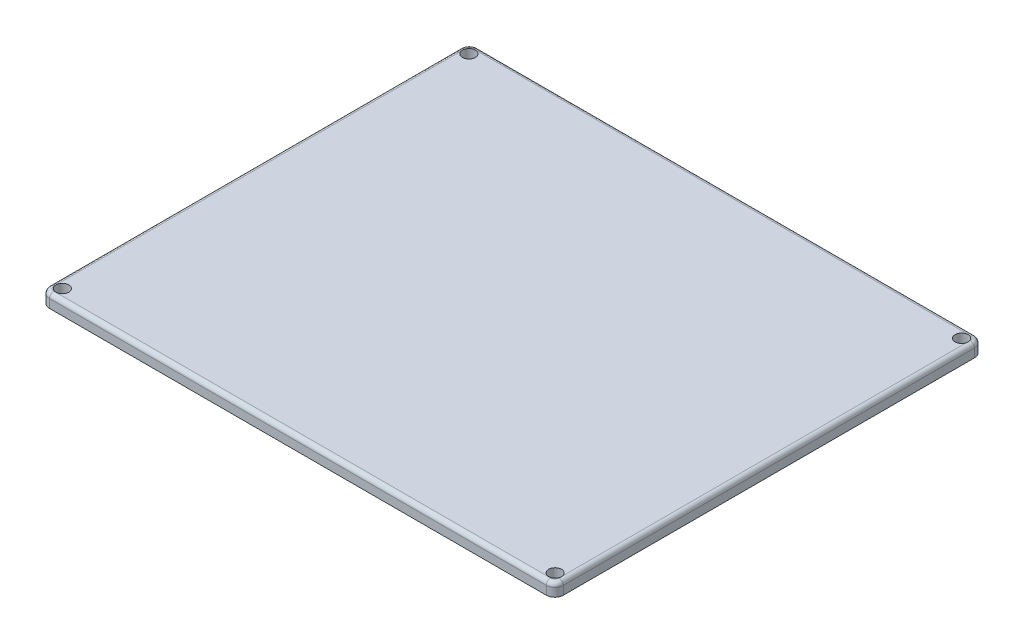
SolidWorks part; units mm, degrees
ref_plane "Front Plane" through (0, 0, 0) normal (0, 0, 1) x (1, 0, 0)
ref_plane "Top Plane" through (0, 0, 0) normal (0, 1, 0) x (1, 0, 0)
ref_plane "Right Plane" through (0, 0, 0) normal (1, 0, 0) x (0, 0, -1)
sketch "Sketch1" plane through (0, 0, 0) normal (0, 1, 0) x (1, 0, 0)
  line L1 (-60, 50) -> (60, 50)
  line L2 (-60, 50) -> (-60, -50)
  line L3 (-60, -50) -> (60, -50)
  line L4 (60, 50) -> (60, -50)
  line L5 (-60, 50) -> (60, -50) construction
  line L6 (-60, -50) -> (60, 50) construction
  point P0 (0, 0)
  dimension "D1" = 120
  dimension "D2" = 100
extrude "Boss-Extrude1" add sketch "Sketch1" along normal blind 3
sketch "Sketch2" plane through (0, 0, 0) normal (0, -1, 0) x (-1, 0, 0)
  line L0 (0, 50) -> (0, -50) construction
  line L1 (-60, 50) -> (60, 50) construction
  line L2 (60, -50) -> (-60, -50) construction
  line L3 (60, 0) -> (-60, 0) construction
  line L4 (60, 50) -> (60, -50) construction
  line L5 (-60, -50) -> (-60, 50) construction
  circle A0 centre (57.529, -47.4651) radius 1.5
  circle A1 centre (57.529, 47.4651) radius 1.5
  circle A2 centre (-57.529, 47.4651) radius 1.5
  circle A3 centre (-57.529, -47.4651) radius 1.5
  dimension "D1" = 3
  dimension "D2" = 3.54
extrude "Cut-Extrude1" cut sketch "Sketch2" against normal through all
fillet "Fillet2" radius 1 4 edges at (-60, 3, 0) (0, 3, 50) (60, 3, 0) (0, 3, -50)
fillet "Fillet4" radius 2 8 edges at (59.7071, 2.7071, -49.7071) (-59.7071, 2.7071, -49.7071) (59.7071, 2.7071, 49.7071) (-59.7071, 2.7071, 49.7071) (-60, 1, 50) (60, 1, 50) (-60, 1, -50) (60, 1, -50)
